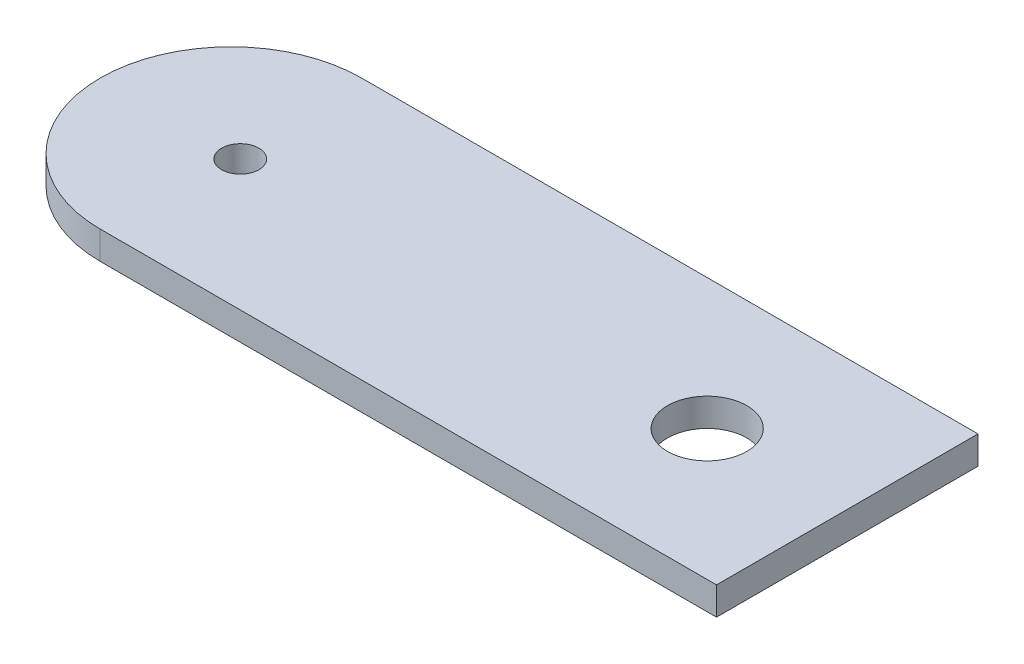
SolidWorks part; units mm, degrees
ref_plane "前视" through (0, 0, 0) normal (0, 0, 1) x (1, 0, 0)
ref_plane "上视" through (0, 0, 0) normal (0, 1, 0) x (1, 0, 0)
ref_plane "右视" through (0, 0, 0) normal (1, 0, 0) x (0, 0, -1)
sketch "草图1" plane through (0, 0, 0) normal (0, 1, 0) x (1, 0, 0)
  line L1 (-40, 14) -> (40, 14)
  line L2 (-40, 14) -> (-40, -14)
  line L3 (-40, -14) -> (40, -14)
  line L4 (40, 14) -> (40, -14)
  line L5 (-40, 14) -> (40, -14) construction
  line L6 (-40, -14) -> (40, 14) construction
  circle A0 centre (25, 0) radius 4.25
  circle A1 centre (-25, 0) radius 2
  point P0 (0, 0)
  dimension "D3" = 4
  dimension "D4" = 8.5
  dimension "D1" = 80
  dimension "D2" = 28
  dimension "D5" = 50
  dimension "D6" = 25
extrude "凸台-拉伸1" add sketch "草图1" along normal blind 3
sketch "草图2" plane through (0, 3, 0) normal (0, 1, 0) x (1, 0, 0)
  text T0 "        <b>     1</b>"
extrude "凸台-拉伸2" [suppressed] add sketch "草图2" along normal blind 0.5
fillet "圆角1" 2 edges at (-40, 1.5, -14) (-40, 1.5, 14) type full round first side face at (0, 1.5, -14) second side face at (0, 1.5, 14) middle face at (-40, 1.5, 0) tangent propagation no
